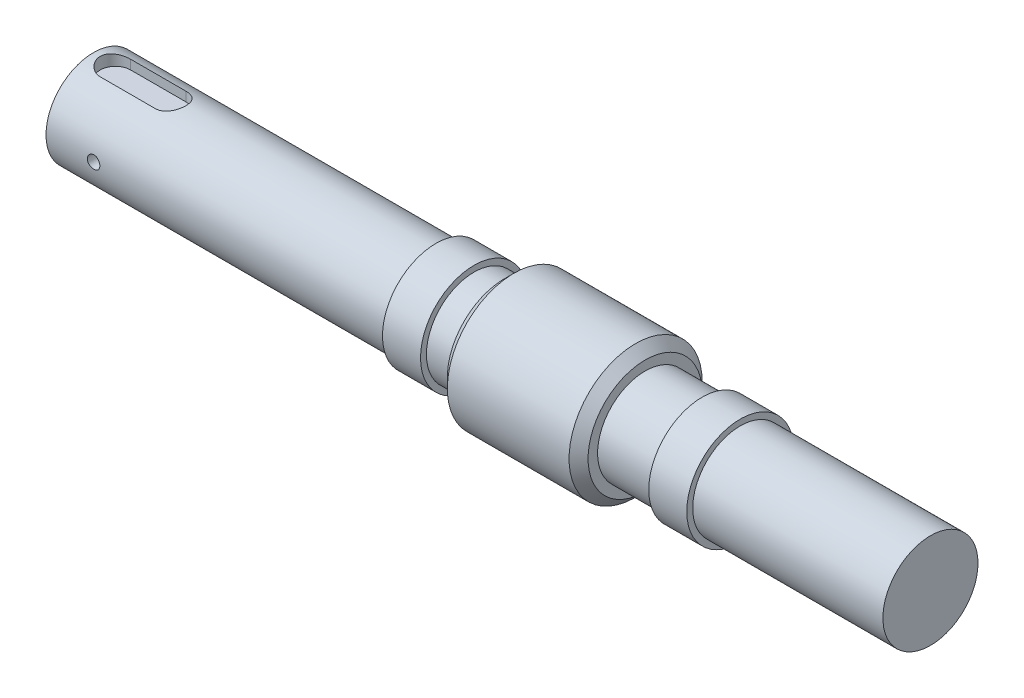
SolidWorks part; units mm, degrees
ref_plane "Frontal" through (0, 0, 0) normal (0, 0, 1) x (1, 0, 0)
ref_plane "Superior" through (0, 0, 0) normal (0, 1, 0) x (1, 0, 0)
ref_plane "Izquierda" through (0, 0, 0) normal (1, 0, 0) x (0, 0, -1)
sketch "Croquis1" plane through (0, 0, 0) normal (1, 0, 0) x (0, 0, -1)
  circle A0 centre (0, 0) radius 35
  dimension "D1" = 70
extrude "Saliente-Extruir1" add sketch "Croquis1" along normal mid plane 74
ref_plane "Plano1" through (7, 0, 0) normal (-1, 0, 0) x (0, 0, 1)
chamfer "Chaflán1" distance 5 angle 45 2 edges at (37, 0, -35) (-37, 0, -35)
sketch "Croquis2" plane through (-37, 0, 0) normal (-1, 0, 0) x (0, 0, 1)
  circle A0 centre (0, 0) radius 25
  dimension "D1" = 50
extrude "Saliente-Extruir2" add sketch "Croquis2" along normal blind 16
sketch "Croquis3" plane through (-53, 0, 0) normal (-1, 0, 0) x (0, 0, 1)
  circle A0 centre (0, 0) radius 28.1
  dimension "D1" = 56.2
extrude "Saliente-Extruir3" add sketch "Croquis3" along normal blind 120
chamfer "Chaflán2" [suppressed] distance 2.5 angle 45
sketch "Croquis4" plane through (37, 0, 0) normal (1, 0, 0) x (0, 0, -1)
  circle A0 centre (0, 0) radius 25
  dimension "D1" = 50
extrude "Saliente-Extruir4" add sketch "Croquis4" along normal blind 30
sketch "Croquis5" plane through (67, 0, 0) normal (1, 0, 0) x (0, 0, -1)
  circle A0 centre (0, 0) radius 28.1
  dimension "D1" = 56.2
extrude "Saliente-Extruir5" add sketch "Croquis5" along normal blind 120
chamfer "Chaflán3" [suppressed] distance 2.5 angle 45
sketch "Croquis6" plane through (-173, 0, 0) normal (-1, 0, 0) x (0, 0, 1)
  circle A0 centre (0, 0) radius 25
  circle A1 centre (0, 0) radius 28.1
extrude "Cortar-Extruir1" cut sketch "Croquis6" against normal blind 100
sketch "Croquis8" plane through (187, 0, 0) normal (1, 0, 0) x (0, 0, -1)
  circle A0 centre (0, 0) radius 25
  circle A1 centre (0, 0) radius 28.1
extrude "Cortar-Extruir2" cut sketch "Croquis8" against normal blind 100
sketch "Croquis9" plane through (-173, 0, 0) normal (-1, 0, 0) x (0, 0, 1)
  circle A0 centre (0, 0) radius 25
  dimension "D1" = 50
extrude "Saliente-Extruir6" add sketch "Croquis9" along normal blind 80
sketch "Croquis10" plane through (0, 0, 0) normal (0, 1, 0) x (1, 0, 0)
  line L0 (-253, 0) -> (-66.718, 0) construction
  line L1 (-253, 25) -> (-253, -25) construction
  line L2 (-241.5, 0) -> (-212.5, 0) construction
  line L3 (-241.5, 8) -> (-212.5, 8)
  line L4 (-241.5, -8) -> (-212.5, -8)
  arc A0 (-241.5, 8) -> (-241.5, -8) centre (-241.5, 0) ccw
  arc A1 (-212.5, -8) -> (-212.5, 8) centre (-212.5, 0) ccw
  point P7 (-227, 0)
  point P12 (-249.5, 0)
  point P13 (-204.5, 0)
  dimension "D1" = 45
  dimension "D2" = 16
  dimension "D3" = 26
extrude "Cortar-Extruir3" cut sketch "Croquis10" along normal blind 6.2 from offset 18.8
hole_wizard "Taladro de margen para M61" positions "Croquis3D2" profile "Croquis12" hole size "M6" standard "DIN"
sketch3d "Croquis3D2"
  line L0 (-253, 0, 0) -> (-253, 48.809, 0) construction
  line L1 (-73, 0, 0) -> (-253, 0, 0) construction
  line L3 (-253, 0, 0) -> (-253, -25, 0) construction
  line L5 (-253, 0, 0) -> (-253, 0, 25) construction
  line L6 (-253, 0, 25) -> (-198.2724, 0, 25) construction
  line L8 (-253, -25, 0) -> (-213.979, -25, 0) construction
  circle A0 centre (-253, 0, 0) radius 25 construction
  point P17 (-278, 0, 0)
  point P35 (-228, 0, 25)
  point P37 (-228, -25, 0)
  dimension "D1" = 25
  dimension "D2" = 25
sketch "Croquis12" plane through (-228, -25, 0) normal (1, 0, 0) x (0, 0, -1)
  line L0 (0, 0) -> (0, 18.9828)
  line L1 (0, 18.9828) -> (3.3, 17)
  line L2 (3.3, 17) -> (3.3, 0)
  line L5 (3.3, 0) -> (0, 0)
  line L10 (0, 18.9828) -> (-3.3, 17) construction
  line L11 (0, -6.35) -> (0, 107.95) construction
  dimension "Diámetro de taladro" = 6.6
  dimension "Profundidad de taladro" = 17
  dimension "Ángulo de perforador" = 118
hole_wizard "Taladro roscado M61" positions "Croquis3D3" profile "Croquis13" tap size "M6" standard "DIN"
sketch3d "Croquis3D3"
  line L0 (-253, 0, 0) -> (-253, 25, 0) construction
  line L1 (-73, 0, 0) -> (-253, 0, 0) construction
  line L3 (-253, 0, 0) -> (-253, -25, 0) construction
  circle A0 centre (-253, 0, 0) radius 25 construction
  circle A1 centre (-253, 0, 0) radius 17.5 construction
  point P2 (-253, -17.5, 0)
  point P11 (-278, 0, 0)
  point P18 (-235.5, 0, 0)
  point P25 (0, 0, 0)
  dimension "D1" = 35
sketch "Croquis13" plane through (-253, -17.5, 0) normal (0, 1, 0) x (0, 0, 1)
  line L0 (0, 0) -> (0, 13)
  line L1 (0, 13) -> (2.5, 11.4978)
  line L2 (2.5, 11.4978) -> (2.5, 0)
  line L5 (2.5, 0) -> (0, 0)
  line L10 (0, 13) -> (-2.5, 11.4978) construction
  line L11 (0, -6.35) -> (0, 107.95) construction
  dimension "Diámetro de perforador para roscar" = 5
  dimension "Profundidad de perforador para roscar" = 13
  dimension "Ángulo de perforador" = 118
cosmetic thread "Rosca de taladro1" parameters "D1"=12, "D2"=6
